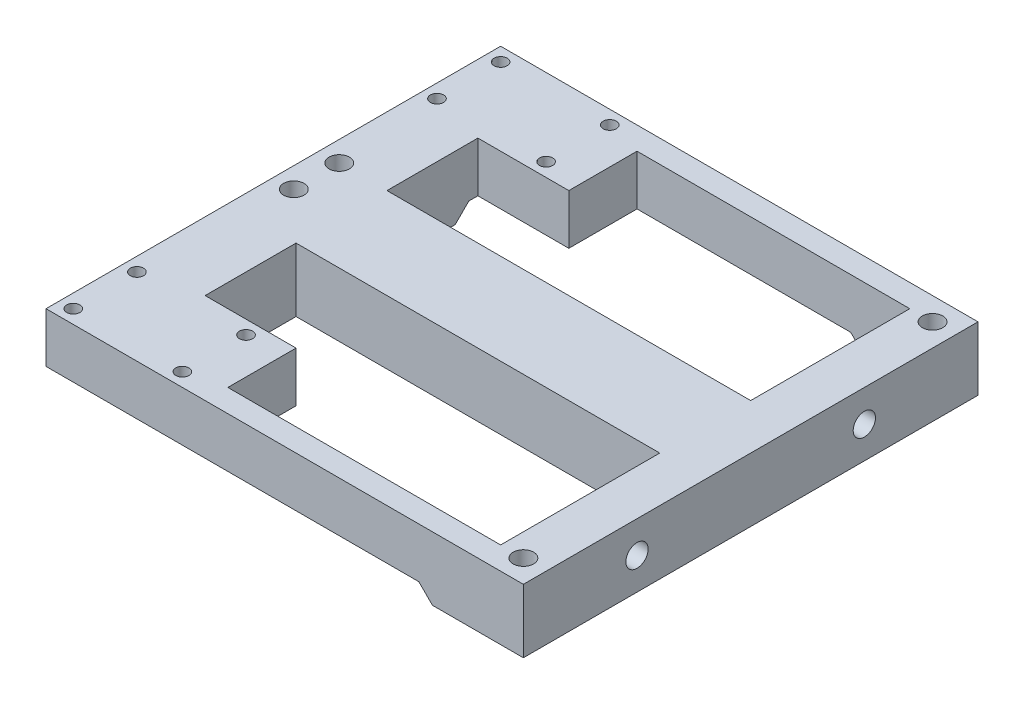
SolidWorks part; units mm, degrees
ref_plane "前视基准面" through (0, 0, 0) normal (0, 0, 1) x (1, 0, 0)
ref_plane "上视基准面" through (0, 0, 0) normal (0, 1, 0) x (1, 0, 0)
ref_plane "右视基准面" through (0, 0, 0) normal (1, 0, 0) x (0, 0, -1)
other "Configuration Table"
sketch "草图1" plane through (0, 0, 0) normal (0, 1, 0) x (1, 0, 0)
  line L1 (0, 0) -> (-105, 0)
  line L2 (0, 0) -> (0, 100)
  line L3 (0, 100) -> (-105, 100)
  line L4 (-105, 0) -> (-105, 100)
  dimension "D1" = 100
  dimension "D2" = 105
extrude "凸台-拉伸1" add sketch "草图1" along normal blind 16
sketch "草图6" plane through (0, 16, 0) normal (0, 1, 0) x (1, 0, 0)
  line L0 (-105, 100) -> (-105, 0) construction
  line L1 (-45.2241, 40) -> (-5, 40)
  line L2 (-70, 20) -> (-70, 5)
  line L3 (-70, 5) -> (-5, 5)
  line L4 (-5, 40) -> (-5, 5)
  line L5 (0, 0) -> (0, 100) construction
  line L6 (-105, 0) -> (0, 0) construction
  line L7 (-105, 50) -> (-60.5255, 50) construction
  line L8 (-70, 95) -> (-5, 95)
  line L9 (-5, 60) -> (-5, 95)
  line L10 (-45.2241, 60) -> (-5, 60)
  line L11 (-70, 80) -> (-70, 95)
  line L12 (-70, 80) -> (-100, 80)
  line L13 (-45.2241, 40) -> (-100, 40)
  line L15 (-70, 20) -> (-100, 20)
  line L16 (-100, 40) -> (-100, 20)
  line L17 (-45.2241, 60) -> (-100, 60)
  line L18 (-100, 60) -> (-100, 80)
  dimension "D1" = 35
  dimension "D2" = 5
  dimension "D3" = 5
  dimension "D4" = 20
  dimension "D5" = 30
  dimension "D6" = 20
extrude "切除-拉伸5" cut sketch "草图6" against normal up to next
sketch "草图8" plane through (0, 16, 0) normal (0, 1, 0) x (1, 0, 0)
  line L0 (-105, 100) -> (-102, 100) construction
  line L1 (0, 100) -> (-105, 100) construction
  line L2 (-102, 100) -> (-102, 97) construction
  line L3 (-102, 97) -> (-78, 97) construction
  line L4 (-78, 97) -> (-78, 83) construction
  line L5 (-78, 83) -> (-102, 83) construction
  line L6 (-105, 50) -> (-51.1245, 50) construction
  line L7 (-105, 100) -> (-105, 0) construction
  line L8 (-78, 17) -> (-102, 17) construction
  line L9 (-78, 3) -> (-78, 17) construction
  line L10 (-102, 3) -> (-78, 3) construction
  line L11 (-102, 0) -> (-102, 3) construction
  line L12 (-105, 0) -> (-102, 0) construction
  circle A0 centre (-102, 97) radius 1.45
  circle A1 centre (-102, 83) radius 1.45
  circle A2 centre (-78, 97) radius 1.45
  circle A3 centre (-78, 83) radius 1.45
  circle A4 centre (-78, 17) radius 1.45
  circle A5 centre (-78, 3) radius 1.45
  circle A6 centre (-102, 17) radius 1.45
  circle A7 centre (-102, 3) radius 1.45
  dimension "D6" = 2.9
  dimension "D7" = 2.9
  dimension "D8" = 2.9
  dimension "D9" = 2.9
  dimension "D1" = 3
  dimension "D2" = 3
  dimension "D3" = 24
  dimension "D4" = 14
  dimension "D5" = 24
extrude "切除-拉伸7" cut sketch "草图8" against normal through all
sketch "草图9" plane through (-5, 0, 0) normal (-1, 0, 0) x (0, 0, 1)
  line L0 (-40, 0) -> (-5, 0) construction
  line L1 (-5, 0) -> (-5, 16) construction
  line L2 (-5, 16) -> (-40, 16) construction
  line L3 (-40, 16) -> (-40, 0) construction
  line L4 (-95, 0) -> (-60, 0) construction
  line L5 (-60, 0) -> (-60, 16) construction
  line L6 (-60, 16) -> (-95, 16) construction
  line L7 (-95, 16) -> (-95, 0) construction
  line L8 (-40, 0) -> (-5, 0)
  line L9 (-5, 0) -> (-5, 16)
  line L10 (-5, 16) -> (-40, 16)
  line L11 (-40, 16) -> (-40, 0)
  line L12 (-95, 0) -> (-60, 0)
  line L13 (-60, 0) -> (-60, 16)
  line L14 (-60, 16) -> (-95, 16)
  line L15 (-95, 16) -> (-95, 0)
extrude "凸台-拉伸2" add sketch "草图9" along normal blind 5
sketch "草图10" plane through (0, 16, 0) normal (0, 1, 0) x (1, 0, 0)
  line L0 (0, 100) -> (0, 95) construction
  line L1 (0, 0) -> (0, 100) construction
  line L2 (0, 95) -> (-5, 95) construction
  line L3 (0, 50) -> (-16.1785, 50) construction
  circle A0 centre (-5, 95) radius 2.25
  circle A1 centre (-5, 5) radius 2.25
  dimension "D3" = 4.5
  dimension "D1" = 5
extrude "切除-拉伸8" cut sketch "草图10" against normal blind 5
sketch "草图12" plane through (-100, 0, 0) normal (1, 0, 0) x (0, 0, -1)
  line L0 (20, 0) -> (40, 0) construction
  line L1 (40, 0) -> (40, 16) construction
  line L2 (40, 16) -> (20, 16) construction
  line L3 (20, 16) -> (20, 0) construction
  line L4 (60, 0) -> (80, 0) construction
  line L5 (80, 0) -> (80, 16) construction
  line L6 (80, 16) -> (60, 16) construction
  line L7 (60, 16) -> (60, 0) construction
  line L8 (20, 0) -> (40, 0)
  line L9 (40, 0) -> (40, 16)
  line L10 (40, 16) -> (20, 16)
  line L11 (20, 16) -> (20, 0)
  line L12 (60, 0) -> (80, 0)
  line L13 (80, 0) -> (80, 16)
  line L14 (80, 16) -> (60, 16)
  line L15 (60, 16) -> (60, 0)
extrude "凸台-拉伸3" add sketch "草图12" along normal blind 10
sketch "草图13" plane through (0, 16, 0) normal (0, 1, 0) x (1, 0, 0)
  line L0 (-105, 50) -> (-100.5, 50) construction
  line L1 (-105, 100) -> (-105, 0) construction
  line L3 (-100.5, 50) -> (-100.5, 60) construction
  circle A0 centre (-100.5, 50) radius 2.25
  circle A1 centre (-100.5, 60) radius 2.25
  dimension "D4" = 4.5
  dimension "D5" = 4.5
  dimension "D3" = 10
  dimension "D6" = 4.5
  dimension "D1" = 4.5
  dimension "D2" = 10
extrude "切除-拉伸10" cut sketch "草图13" against normal blind 5
sketch "草图14" plane through (0, 0, 0) normal (0, -1, 0) x (1, 0, 0)
  line L4 (0, -100) -> (0, 0)
  line L5 (0, 0) -> (-105, 0)
  line L6 (-105, 0) -> (-105, -100)
  line L7 (-105, -100) -> (0, -100)
  line L9 (0, 0) -> (-105, 0)
  line L10 (-105, 0) -> (-105, -100)
  line L11 (-105, -100) -> (0, -100)
  line L13 (0, -100) -> (0, 0)
  dimension "D1" = 0
extrude "切除-拉伸11" cut sketch "草图14" against normal blind 2
sketch "草图15" plane through (0, 11, 0) normal (0, 1, 0) x (1, 0, 0)
  circle A0 centre (-5, 5) radius 1.5
  circle A1 centre (-5, 95) radius 1.5
  circle A2 centre (-100.5, 60) radius 1.5
  circle A3 centre (-100.5, 50) radius 1.5
  dimension "D1" = 3
  dimension "D2" = 3
  dimension "D3" = 3
  dimension "D4" = 3
extrude "切除-拉伸12" cut sketch "草图15" against normal blind 4
sketch "草图16" plane through (0, 2, 0) normal (0, -1, 0) x (1, 0, 0)
  line L0 (-10, -40) -> (-10, -5) construction
  line L1 (-105, 0) -> (-20, 0)
  line L2 (-105, 0) -> (-105, -25)
  line L3 (-105, -25) -> (-20, -25)
  line L4 (-20, 0) -> (-20, -25)
  line L5 (-20, -75) -> (-105, -75)
  line L6 (-20, -75) -> (-20, -100)
  line L7 (-20, -100) -> (-105, -100)
  line L8 (-105, -75) -> (-105, -100)
  line L9 (-10, -95) -> (-10, -60) construction
  dimension "D1" = 10
  dimension "D2" = 10
extrude "切除-拉伸13" cut sketch "草图16" against normal blind 3
chamfer "倒角1" distance 3 angle 45 4 edges at (-20, 5, -2.5) (-97.5, 5, -25) (-97.5, 5, -75) (-20, 5, -97.5)
sketch "草图17" plane through (-105, 0, 0) normal (-1, 0, 0) x (0, 0, 1)
  line L0 (0, 9) -> (-55.4, 9) construction
  line L1 (0, 16) -> (0, 5) construction
  line L2 (-100, 16) -> (0, 16) construction
  circle A0 centre (-55.4, 9) radius 2.25
  dimension "D2" = 4.5
  dimension "D1" = 55.4
  dimension "D3" = 7
extrude "切除-拉伸14" cut sketch "草图17" against normal blind 5
sketch "草图18" plane through (-100, 0, 0) normal (-1, 0, 0) x (0, 0, 1)
  circle A0 centre (-55.4, 9) radius 1.5
  dimension "D1" = 3
extrude "切除-拉伸15" cut sketch "草图18" against normal blind 4
sketch "草图21" plane through (0, 0, 0) normal (1, 0, 0) x (0, 0, -1)
  line L0 (100, 16) -> (100, 2) construction
  line L1 (0, 16) -> (100, 16) construction
  line L2 (0, 16) -> (0, 2) construction
  circle A0 centre (25, 9) radius 2.45
  circle A1 centre (75, 9) radius 2.45
  dimension "D1" = 25
  dimension "D2" = 7
  dimension "D3" = 4.9
  dimension "D4" = 4.9
  dimension "D5" = 7
  dimension "D6" = 25
extrude "切除-拉伸17" cut sketch "草图21" against normal blind 13.2
